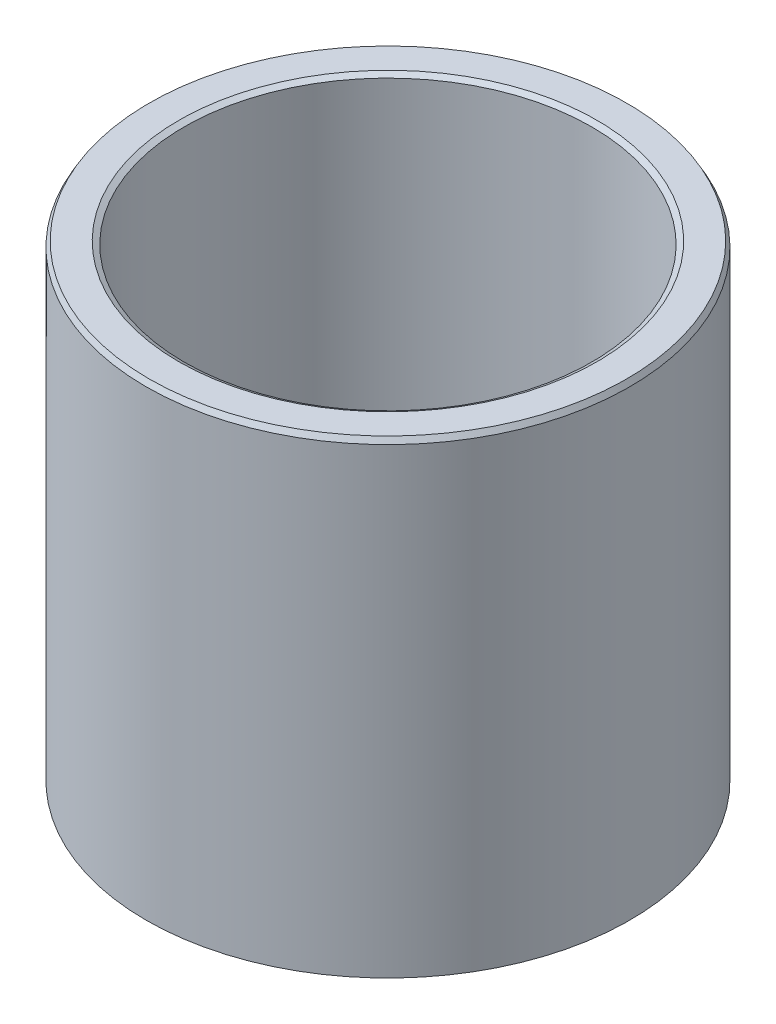
SolidWorks part; units mm, degrees
ref_plane "Front Plane" through (0, 0, 0) normal (0, 0, 1) x (1, 0, 0)
ref_plane "Top Plane" through (0, 0, 0) normal (0, 1, 0) x (1, 0, 0)
ref_plane "Right Plane" through (0, 0, 0) normal (1, 0, 0) x (0, 0, -1)
sketch "Sketch1" plane through (0, 0, 0) normal (0, 1, 0) x (1, 0, 0)
  circle A0 centre (0, 0) radius 42.5
  dimension "SLEEVE_OD" = 85
extrude "Boss-Extrude1" add sketch "Sketch1" along normal blind 82.649
sketch "Sketch2" plane through (0, 0, 0) normal (0, 1, 0) x (1, 0, 0)
  circle A0 centre (0, 0) radius 35.8121
  dimension "BORE_D" = 71.6242
extrude "Cut-Extrude1" cut sketch "Sketch2" along normal through all
chamfer "Chamfer1" distance 0.9367 angle 29.384 4 edges at (0, 82.649, 35.8121) (0, 0, 35.8121) (0, 0, 42.5) (0, 82.649, 42.5) first distance on face at (0, 82.649, 35.8121) first distance on face at (0, 0, 35.8121) first distance on face at (0, 82.649, 42.5)
